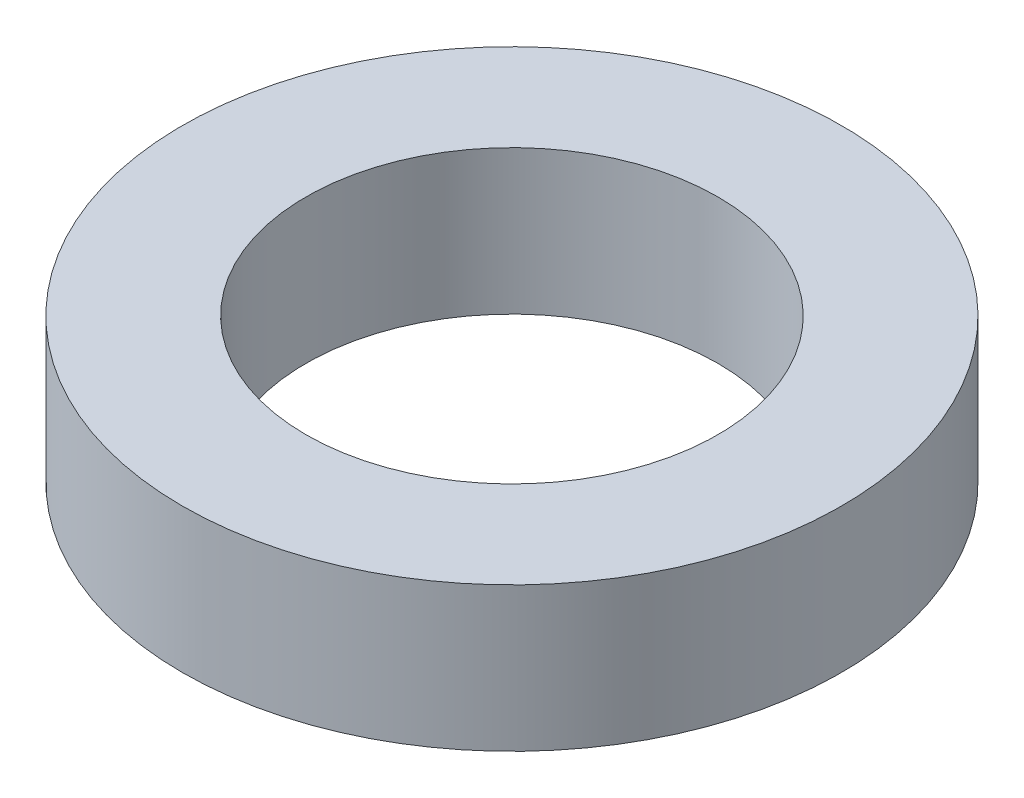
SolidWorks part; units mm, degrees
ref_plane "Front Plane" through (0, 0, 0) normal (0, 0, 1) x (1, 0, 0)
ref_plane "Top Plane" through (0, 0, 0) normal (0, 1, 0) x (1, 0, 0)
ref_plane "Right Plane" through (0, 0, 0) normal (1, 0, 0) x (0, 0, -1)
sketch "Sketch1" plane through (0, 0, 0) normal (0, 1, 0) x (1, 0, 0)
  circle A0 centre (0, 0) radius 16
  circle A1 centre (0, 0) radius 10
  dimension "D1" = 20
  dimension "D2" = 32
extrude "Boss-Extrude1" add sketch "Sketch1" along normal mid plane 7
equation "\"Ns\" = 48"
equation "\"Np_b\" = 48"
equation "\"Np_s\" = 32"
equation "\"Nr_b\" = 144"
equation "\"num_planet\" = 4"
equation "\"module\" = 0.6"
equation "\"fw_p_b\" = 34.81179682049524"
equation "\"fw_r_b\" = 34.81179682049524"
equation "\"fw_s_calc\" = 7.664359769718526"
equation "\"fw_r_s\" = 28.731545005724083"
equation "\"fw_p_s\" = 30.231545005724083"
equation "\"fw_s_used\" = 72.54334182621932"
equation "\"pressure_angle\" = 20.0"
equation "\"motor_OD\" = 106.8"
equation "\"motor_height\" = 47.6"
equation "\"motor_mount_hole_PCD\" = 40"
equation "\"motor_mount_hole_dia\" = 5"
equation "\"motor_mount_hole_num\" = 4"
equation "\"wire_slot_dist_from_center\" = 45.5"
equation "\"wire_slot_length\" = 10"
equation "\"wire_slot_radius\" = 3"
equation "\"motor_output_hole_PCD\" = 23"
equation "\"motor_output_hole_dia\" = 4"
equation "\"motor_output_hole_num\" = 4"
equation "\"h_a\" = 0.6"
equation "\"h_f\" = 0.75"
equation "\"clr_tip_root\" = 0.15000000000000002"
equation "\"dp_r_b\" = 86.39999999999999"
equation "\"db_r_b\" = 81.18944243590248"
equation "\"alpha_r_b\" = 0.8539582918412414"
equation "\"beta_r_b\" = 2.957916583682483"
equation "\"bearing_ID\" = 65"
equation "\"bearing_OD\" = 85"
equation "\"bearing_height\" = 10"
equation "\"clearance_planet\" = 1.5"
equation "\"case_dist\" = 6.5"
equation "\"Motor_case_OD_max\" = 131.3"
equation "\"case_mounting_PCD\" = 123.8"
equation "\"bearing mount thickness\" = 8"
equation "\"case_mounting_hole_dia\" = 3"
equation "\"output_mounting_PCD\" = 93"
equation "\"output_mounting_hole_dia\" = 4"
equation "\"clearance_case_mount_holes_shell_thickness\" = 1"
equation "\"motor_case_OD_base\" = 121.8"
equation "\"sec_carrier_thickness\" = 5"
equation "\"sun_coupler_hub_thickness\" = 4"
equation "\"clearance_sun_coupler_sec_carrier\" = 1.5"
equation "\"clearance_motor_and_case\" = 5"
equation "\"Motor_case_thickness\" = 2.5"
equation "\"Motor_case_ID\" = 116.8"
equation "\"case_mounting_hole_shift\" = 1.0"
equation "\"output_mounting_nut_wrench_size\" = 7"
equation "\"output_mounting_nut_thickness\" = 3.2"
equation "\"case_mounting_hole_allen_socket_dia\" = 5.5"
equation "\"output_mounting_nut_depth\" = 3"
equation "\"case_mounting_bolt_depth\" = 4.5"
equation "\"ring_radial_thickness\" = 5"
equation "\"ring_OD_b\" = 96.39999999999999"
equation "\"ring_to_chamfer_clearance\" = 1.5"
equation "\"Motor_case_OD_base_to_chamfer\" = 5"
equation "\"pattern_offset_from_motor_case_OD_base\" = 3"
equation "\"pattern_bulge_dia\" = 3"
equation "\"pattern_num_bulge\" = 18"
equation "\"pattern_depth\" = 2"
equation "\"case_mounting_wrench_size\" = 5.5"
equation "\"case_mounting_nut_clearance\" = 2"
equation "\"base_plate_thickness\" = 4"
equation "\"case_mounting_nut_thickness\" = 2.4"
equation "\"case_mounting_surface_height\" = 4"
equation "\"central_hole_offset_from_motor_mount_PCD\" = 5"
equation "\"driver_upper_holes_dist_from_center\" = 29"
equation "\"driver_lower_holes_dist_from_center\" = 13"
equation "\"driver_side_holes_dist_from_center\" = 22.5"
equation "\"driver_mount_holes_dia\" = 3"
equation "\"driver_mount_inserts_OD\" = 4.8"
equation "\"driver_mount_thickness\" = 1.5"
equation "\"driver_mount_height\" = 6"
equation "\"air_flow_hole_offset\" = 3"
equation "\"pressure angle\" = 20.0"
equation "\"h_b\" = 0.75"
equation "\"planet_pin_bolt_dia\" = 5"
equation "\"planet_pin_socket_head_dia\" = 8.5"
equation "\"carrier_PCD\" = 57.599999999999994"
equation "\"planet_shaft_dia\" = 8"
equation "\"planet_shaft_step_offset\" = 1"
equation "\"carrier_trapezoidal_support_sun_offset\" = 5"
equation "\"carrier_trapezoidal_support_hole_PCD_offset_bearing_ID\" = 4"
equation "\"carrier_trapezoidal_support_hole_dia\" = 3"
equation "\"carrier_trapezoidal_support_hole_socket_head_dia\" = 5.5"
equation "\"carrier_bearing_step_width\" = 1.5"
equation "\"standard_clearance_1_5mm\" = 1.5"
equation "\"standard_fillet_1_5mm\" = 1.5"
equation "\"sun_shaft_bearing_ID\" = 8"
equation "\"sun_shaft_bearing_OD\" = 16"
equation "\"sun_shaft_bearing_width\" = 5"
equation "\"standard_bearing_insertion_chamfer\" = 0.5"
equation "\"carrier_trapezoidal_support_hole_wrench_size\" = 5.5"
equation "\"planet_pin_bolt_wrench_size\" = 8"
equation "\"planet_bearing_OD\" = 12"
equation "\"planet_bearing_width\" = 3.5"
equation "\"planet_bore\" = 10"
equation "\"dp_s\" = 28.799999999999997"
equation "\"db_s\" = 27.06314747863416"
equation "\"alpha_s\" = 0.8539582918412343"
equation "\"beta_s\" = 2.0420834163175314"
equation "\"dp_p_b\" = 28.799999999999997"
equation "\"db_p_b\" = 27.06314747863416"
equation "\"alpha_p_b\" = 0.8539582918412343"
equation "\"beta_p_b\" = 2.0420834163175314"
equation "\"sun_hub_dia\" = 30.0"
equation "\"sun_central_bolt_dia\" = 5"
equation "\"sun_central_bolt_socket_head_dia\" = 8.5"
equation "\"motor_output_hole_CSK_OD\" = 8"
equation "\"motor_output_hole_CSK_head_height\" = 2.0"
equation "\"bearing_retainer_thickness\" = 2"
equation "\"dp_p_s\" = 19.2"
equation "\"db_p_s\" = 18.04209831908944"
equation "\"alpha_p_s\" = 0.8539582918412556"
equation "\"beta_p_s\" = 3.917083416317489"
equation "\"Nr_s\" = 128"
equation "\"clr_tip_root_s\" = 0.15000000000000002"
equation "\"dp_r_s\" = 76.8"
equation "\"db_r_s\" = 72.16839327635776"
equation "\"alpha_r_s\" = 0.8539582918412556"
equation "\"beta_r_s\" = 3.114166583682511"
equation "\"small_ring_case_thickness\" = 4"
equation "\"carrier_thickness\" = 4"
equation "\"small_ring_output_wall_thickness\" = 5"
equation "\"small_ring_output_wall_to_bearing_shaft_attachement_hole_dia\" = 4"
equation "\"small_ring_output_wall_to_bearing_shaft_attachement_hole_depth\" = 6.5"
equation "\"small_ring_output_wall_to_bearing_shaft_attachement_nut_wrench\" = 7"
equation "\"small_ring_output_wall_to_bearing_shaft_attachement_nut_thickness\" = 3.2"
equation "\"small_ring_output_wall_to_bearing_shaft_attachement_hole_pcd\" = 12"
equation "\"small_ring_output_wall_to_bearing_shaft_attachement_hole_num\" = 3"
equation "\"small_ring_output_wall_to_bearing_shaft_attachement_hole_CSK_OD\" = 8"
equation "\"small_ring_output_wall_to_bearing_shaft_attachement_hole_CSK_head_height\" = 2.0"
equation "\"carrier_small_ring_inner_bearing_ID\" = 20"
equation "\"carrier_small_ring_inner_bearing_OD\" = 32"
equation "\"carrier_small_ring_inner_bearing_height\" = 7"
equation "\"carrier_small_ring_inner_bearing_flap\" = 2"
equation "\"D1@Boss-Extrude1\"=\"carrier_small_ring_inner_bearing_height\""
equation "\"D1@Sketch1\"=\"carrier_small_ring_inner_bearing_ID\""
equation "\"D2@Sketch1\"=\"carrier_small_ring_inner_bearing_OD\""
